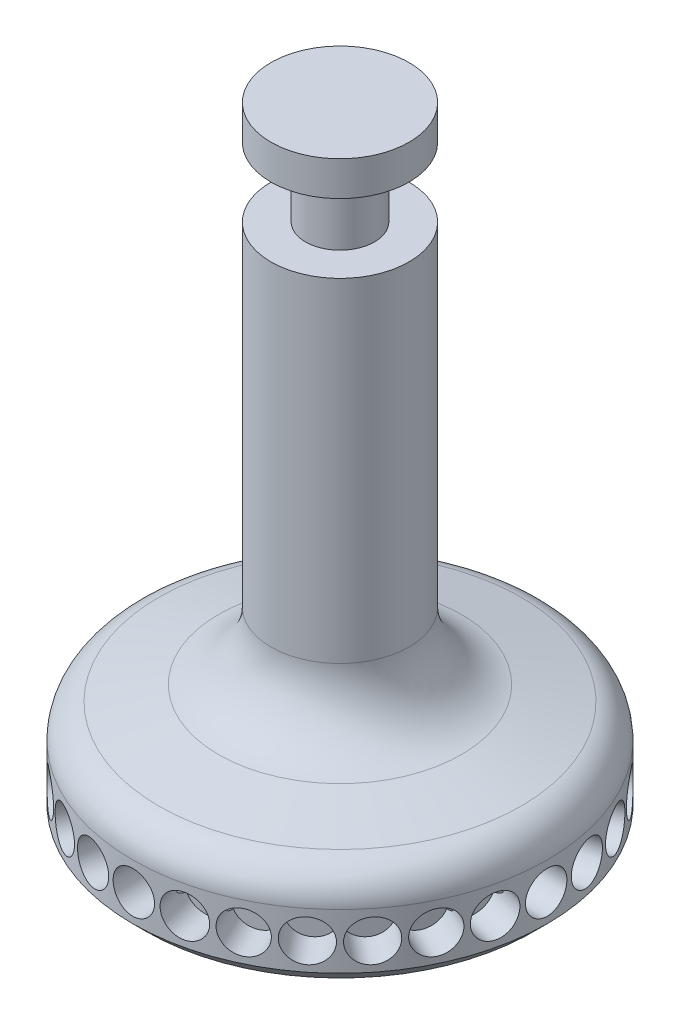
SolidWorks part; units mm, degrees
material "ABS"
ref_plane "Front Plane" through (0, 0, 0) normal (0, 0, 1) x (1, 0, 0)
ref_plane "Top Plane" through (0, 0, 0) normal (0, 1, 0) x (1, 0, 0)
ref_plane "Right Plane" through (0, 0, 0) normal (1, 0, 0) x (0, 0, -1)
sketch "Sketch1" plane through (0, 0, 0) normal (1, 0, 0) x (0, 0, -1)
  line L0 (0, 0) -> (0, -50) construction
  line L3 (26.2096, -35.1485) -> (17.5808, -32.9971)
  line L4 (10, -23.2942) -> (10, 0)
  line L5 (10, 0) -> (0, 0)
  line L6 (30, -40) -> (0, -40) construction
  line L7 (0, 0) -> (0, -50)
  line L8 (0, -50) -> (28, -50)
  line L9 (30, -48) -> (30, -40)
  line L10 (28, -50) -> (30, -48)
  arc A0 (17.5808, -32.9971) -> (10, -23.2942) centre (20, -23.2942) cw
  arc A1 (30, -40) -> (26.2096, -35.1485) centre (25, -40) ccw
  point P12 (30, -50)
  dimension "D4" = 10
  dimension "D5" = 5
  dimension "D1" = 20
  dimension "D2" = 30
  dimension "D3" = 10
  dimension "D6" = 50
  dimension "D7" = 14
revolve "Revolve3" add sketch "Sketch1" angle 360 about L7 other way angle 360
sketch "Sketch3" plane through (0, 0, 0) normal (1, 0, 0) x (0, 0, -1)
  circle A0 centre (0, -44.0545) radius 3
extrude "Cut-Extrude1" cut sketch "Sketch3" against normal blind 25 from offset 50
pattern_circular "CirPattern1" count 28 over 360 about axis through (0, -48, 0) along (0, 1, 0) of "Cut-Extrude1"
sketch "Sketch4" plane through (0, 0, 0) normal (0, 1, 0) x (1, 0, 0)
  circle A0 centre (0, 0) radius 5
  circle M1 centre (0, 0) radius 10
extrude "Boss-Extrude1" add sketch "Sketch4" along normal blind 25 contours A0 M1 | A0 region at (0, 0, 0) region at (-9.7172, 0, 0)
extrude "Boss-Extrude2" add sketch "Sketch4<3>" along normal blind 40 contours A0 | A0 region at (0, 0, 0)
sketch "Sketch4<3>" plane through (0, 0, 0) normal (0, 1, 0) x (1, 0, 0) same geometry as "Sketch4"
sketch "Sketch5" plane through (0, 40, 0) normal (0, 1, 0) x (1, 0, 0)
  circle A2 centre (0, 0) radius 10
  circle A3 centre (0, 0) radius 10
  dimension "D1" = 0
extrude "Boss-Extrude3" add sketch "Sketch5" against normal blind 5
